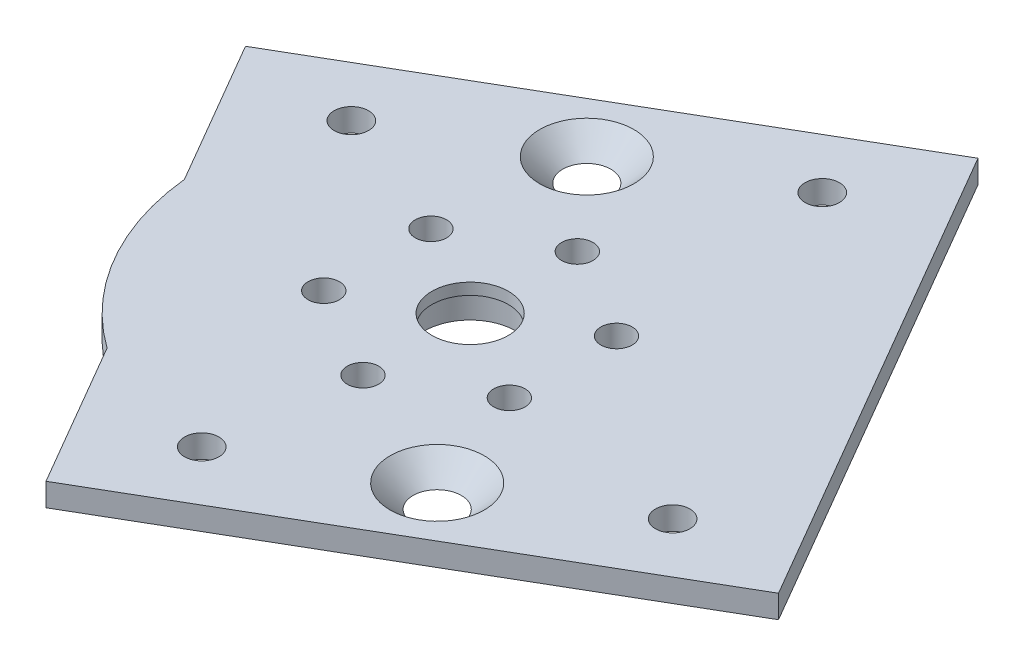
SolidWorks part; units mm, degrees
material "6061 合金"
ref_plane "前视基准面" through (0, 0, 0) normal (0, 0, 1) x (1, 0, 0)
ref_plane "上视基准面" through (0, 0, 0) normal (0, 1, 0) x (1, 0, 0)
ref_plane "右视基准面" through (0, 0, 0) normal (1, 0, 0) x (0, 0, -1)
sketch "草图1" plane through (0, 0, 0) normal (0, 1, 0) x (1, 0, 0)
  circle A0 centre (0, 0) radius 34
  circle A1 centre (0, 0) radius 14 construction
  circle A2 centre (0, 14) radius 2.05
  circle A3 centre (12.1244, 7) radius 2.05
  circle A4 centre (12.1244, -7) radius 2.05
  circle A5 centre (0, -14) radius 2.05
  circle A6 centre (-12.1244, -7) radius 2.05
  circle A7 centre (-12.1244, 7) radius 2.05
  circle A10 centre (0, 0) radius 6
  point P23 (0, 0)
  dimension "D1" = 68
  dimension "D2" = 28
  dimension "D3" = 4.1
  dimension "D5" = 12
  dimension "D4" = 6
extrude "凸台-拉伸1" add sketch "草图1" along normal blind 3
ref_plane "基准面1" through (0, 3, 0) normal (0, 1, 0) x (1, 0, 0)
ref_plane "基准面2" through (0, 0, 0) normal (0, -1, 0) x (-1, 0, 0)
sketch "草图5" plane through (0, 3, 0) normal (0, 1, 0) x (1, 0, 0)
  circle A0 centre (0, 0) radius 5
  circle A1 centre (0, 0) radius 6.5
  dimension "D1" = 10
  dimension "D2" = 13
extrude "凸台-拉伸4" add sketch "草图5" against normal blind 1.5
sketch "草图6" plane through (0, 0, 0) normal (0, -1, 0) x (-1, 0, 0)
  circle A0 centre (0, 0) radius 6
  circle A1 centre (0, 0) radius 7
  dimension "D1" = 14
  dimension "D2" = 12
extrude "凸台-拉伸5" add sketch "草图6" along normal blind 2
ref_plane "基准面3" through (0, 3, 0) normal (0, 1, 0) x (1, 0, 0)
sketch "草图8" plane through (0, 3, 0) normal (0, 1, 0) x (1, 0, 0)
  line L0 (51.8096, -11.5226) -> (15.6239, 50.7237)
  line L1 (51.8096, -11.5226) -> (-8.7076, -46.7031)
  line L2 (15.6239, 50.7237) -> (-44.8933, 15.5432)
  line L3 (-8.7076, -46.7031) -> (-44.8933, 15.5432)
  circle A0 centre (0, 0) radius 34
extrude "凸台-拉伸6" add sketch "草图8" against normal blind 3 contours A0 L3 L1 L0 L2 region at (20.8611, 3, 27.9261)
ref_plane "基准面4" through (0, 0, 0) normal (0, -1, 0) x (-1, 0, 0)
sketch "草图9" plane through (0, 0, 0) normal (0, -1, 0) x (-1, 0, 0)
  circle A0 centre (-9.3405, 36.6607) radius 2.25
  circle A1 centre (-36.4797, -10.024) radius 2.25
  circle A2 centre (29.5635, 14.0446) radius 2.25
  circle A3 centre (2.4242, -32.6401) radius 2.25
  circle A4 centre (10.1115, 25.3527) radius 3.05
  circle A5 centre (-17.0278, -21.332) radius 3.05
  dimension "D1" = 4.5
  dimension "D2" = 6.1
  dimension "D3" = 4.5
  dimension "D4" = 4.5
  dimension "D5" = 6.1
  dimension "D6" = 4.5
extrude "切除-拉伸1" cut sketch "草图9" against normal blind 3
chamfer "倒角2" distance 3.1 angle 45 2 edges at (17.0278, 3, 18.282) (-10.1115, 3, -28.4027)
